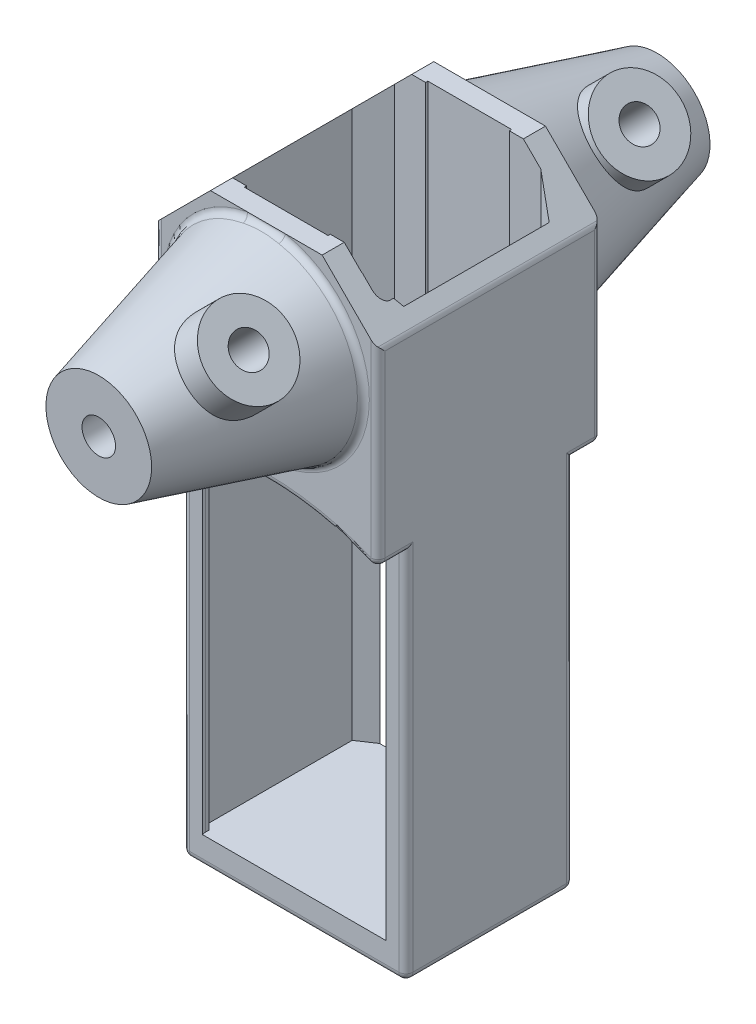
SolidWorks part; units mm, degrees
ref_plane "Front Plane" through (0, 0, 0) normal (0, 0, 1) x (1, 0, 0)
ref_plane "Top Plane" through (0, 0, 0) normal (0, 1, 0) x (1, 0, 0)
ref_plane "Right Plane" through (0, 0, 0) normal (1, 0, 0) x (0, 0, -1)
sketch "Sketch1" plane through (0, 0, 0) normal (0, 1, 0) x (1, 0, 0)
  line L0 (4.7625, -10.1854) -> (8.3298, -10.1854)
  line L5 (-4.7625, 10.1854) -> (-4.7625, 10.4394)
  line L6 (-12.7, -12.7) -> (12.7, -12.7)
  line L7 (4.7625, 10.1854) -> (8.3298, 10.1854)
  line L8 (-8.3298, 10.1854) -> (-11.2014, 8.271)
  line L9 (-8, 10.1) -> (-11, 8.1) construction
  line L10 (0, 0) -> (-11.2014, 0) construction
  line L11 (0, 0) -> (0, 10.4394) construction
  line L12 (-8.3298, -10.1854) -> (-8.3769, -10.154)
  line L13 (8.3298, -10.1854) -> (8.3769, -10.154)
  line L14 (8.3298, 10.1854) -> (11.2014, 8.271)
  line L15 (-8.3298, 10.1854) -> (-4.7625, 10.1854)
  line L16 (-12.7, 12.7) -> (-12.7, -12.7)
  line L17 (12.7, 12.7) -> (12.7, -12.7)
  line L34 (-10.504, -8.7359) -> (-11.2014, -8.271)
  line L35 (8.3769, -10.154) -> (9.4165, -10.154)
  line L36 (9.5863, -10.1409) -> (9.6154, -10.1409)
  line L37 (-9.5863, -10.1409) -> (-9.6154, -10.1409)
  line L38 (-8.75, -10.154) -> (-9.4165, -10.154)
  line L39 (-10.504, -9.1) -> (-10.504, -8.9)
  line L40 (-9.5863, -10.1409) -> (-9.6154, -10.1409)
  line L41 (-8.3769, -10.154) -> (-9.4165, -10.154)
  line L42 (-10.504, -9.1) -> (-10.504, -8.7359)
  line L43 (10.504, -9.1) -> (10.504, -8.7359)
  line L44 (10.504, -8.7359) -> (11.2014, -8.271)
  line L284 (-12.7, 12.7) -> (12.7, 12.7)
  line L286 (-12.7, -12.7) -> (12.7, 12.7) construction
  line L287 (-12.7, 12.7) -> (12.7, -12.7) construction
  line L288 (-8.3298, -10.1854) -> (-4.7625, -10.1854)
  line L289 (-11.2014, -8.271) -> (-11.2014, 8.271)
  line L291 (11.2014, -8.271) -> (11.2014, 8.271)
  line L326 (-4.7625, 10.4394) -> (4.7625, 10.4394)
  line L327 (4.7625, 10.4394) -> (4.7625, 10.1854)
  line L328 (-4.7625, -10.1854) -> (-4.7625, -10.4394)
  line L335 (-4.7625, -10.4394) -> (4.7625, -10.4394)
  line L338 (4.7625, -10.4394) -> (4.7625, -10.1854)
  arc A7 (9.5863, -10.1409) -> (9.4165, -10.154) centre (9.4168, -9.0458) cw
  arc A8 (-9.5863, -10.1409) -> (-9.4165, -10.154) centre (-9.4168, -9.0458) ccw
  arc A9 (-10.504, -9.1) -> (-9.6154, -10.1409) centre (-9.45, -9.1) ccw
  arc A10 (-9.5863, -10.1409) -> (-9.4165, -10.154) centre (-9.4168, -9.0458) ccw
  arc A11 (-10.504, -9.1) -> (-9.6154, -10.1409) centre (-9.45, -9.1) ccw
  arc A12 (10.504, -9.1) -> (9.6154, -10.1409) centre (9.45, -9.1) cw
  point P0 (0, 0)
  point P6 (0, 0)
  point P15 (0, 10.4394)
  point P23 (0, -10.4394)
  dimension "D1" = 25.4
  dimension "D2" = 25.4
  dimension "D3" = 0.254
  dimension "D5" = 9.525
  dimension "D6" = 22.4028
  dimension "D7" = 0.254
  dimension "D8" = 20.3708
  dimension "D9" = 0.254
  dimension "D15" = 0.254
extrude "Boss-Extrude1" add sketch "Sketch1" along normal blind 67.056
sketch "Sketch4" plane through (0, 0, 0) normal (0, -1, 0) x (-1, 0, 0)
  line L1 (12.7, -12.7) -> (-12.7, -12.7)
  line L2 (12.7, -12.7) -> (12.7, 12.7)
  line L3 (12.7, 12.7) -> (-12.7, 12.7)
  line L4 (-12.7, -12.7) -> (-12.7, 12.7)
extrude "Boss-Extrude4" add sketch "Sketch4" along normal blind 3.175
sketch "Sketch5" plane through (0, 0, -12.7) normal (0, 0, -1) x (-1, 0, 0)
  circle A0 centre (0, 11.43) radius 30.1625
  dimension "D2" = 60.325
  dimension "D1" = 11.43
extrude "Cut-Extrude1" cut sketch "Sketch5" against normal blind 3.175
mirror "Mirror1" about plane through (0, 0, 0) normal (0, 0, 1) of "Cut-Extrude1"
sketch "Sketch7" plane through (0, 0, 12.7) normal (0, 0, 1) x (1, 0, 0)
  circle A0 centre (0, 55.5371) radius 11.1125
  circle A1 centre (0, 11.0871) radius 4.7625 construction
  dimension "D2" = 22.225
  dimension "D1" = 44.45
extrude "Boss-Extrude6" add sketch "Sketch7" along normal blind 19.05 draft 15
sketch "Sketch8" plane through (0, 0, 31.75) normal (0, 0, 1) x (1, 0, 0)
  circle A0 centre (0, 55.5371) radius 1.905
  dimension "D1" = 3.81
extrude "Cut-Extrude2" cut sketch "Sketch8" against normal blind 12.7
ref_plane "Plane1" through (29.1156, 29.1156, 0) normal (-0.7071, -0.7071, 0) x (0, 0, 1)
sketch "Sketch9" plane through (29.1156, 29.1156, 0) normal (-0.7071, -0.7071, 0) x (0, 0, 1)
  line L0 (31.75, 33.2626) -> (31.75, 45.2787) construction
  line L1 (22.225, 47.8309) -> (22.225, 30.7104) construction
  line L2 (31.75, 45.2787) -> (12.7, 50.3832) construction
  line L3 (12.7, 28.1582) -> (31.75, 33.2626) construction
  circle A0 centre (22.225, 39.2707) radius 1.905
  point P2 (22.225, 39.2707)
  dimension "D1" = 3.81
  dimension "D2" = 9.525
extrude "Cut-Extrude3" cut sketch "Sketch9" against normal through all from offset 0.7937 offset against normal yes
sketch "Sketch10" plane through (29.1156, 29.1156, 0) normal (-0.7071, -0.7071, 0) x (0, 0, 1)
  circle A0 centre (22.225, 39.2707) radius 4.7625
  circle A1 centre (22.225, 39.2707) radius 1.905 construction
  circle A2 centre (22.225, 39.2707) radius 1.905
  dimension "D1" = 9.525
extrude "Boss-Extrude7" add sketch "Sketch10" against normal blind 7.9375 from offset 0.7937 offset against normal yes
mirror "Mirror3" about plane through (0, 0, 0) normal (0, 0, 1) of "Cut-Extrude3", "Boss-Extrude7", "Boss-Extrude6", "Cut-Extrude2"
chamfer "Chamfer3" distance 6.35 angle 45 2 edges at (-12.7, 67.056, 0) (12.7, 67.056, 0)
fillet "Fillet1" radius 0.7937 22 edges at (11.1125, 55.5371, -12.7) (11.1125, 55.5371, 12.7) (0, -3.175, -9.525) (0, -3.175, 9.525) (-12.7, 38.7885, 11.1125) (-12.7, 17.8067, 9.525) (-12.7, -3.175, 0) (-12.7, 17.8067, -9.525) (-12.7, 38.7885, -11.1125) (-12.7, 49.7472, -12.7) (-12.7, 60.706, 0) (-12.7, 49.7472, 12.7) (12.7, 38.7885, -11.1125) (12.7, 17.8067, -9.525) (12.7, -3.175, 0) (12.7, 17.8067, 9.525) (12.7, 38.7885, 11.1125) (12.7, 49.7472, 12.7) (12.7, 60.706, 0) (12.7, 49.7472, -12.7) (0, 41.5925, 12.7) (0, 41.5925, -12.7)
